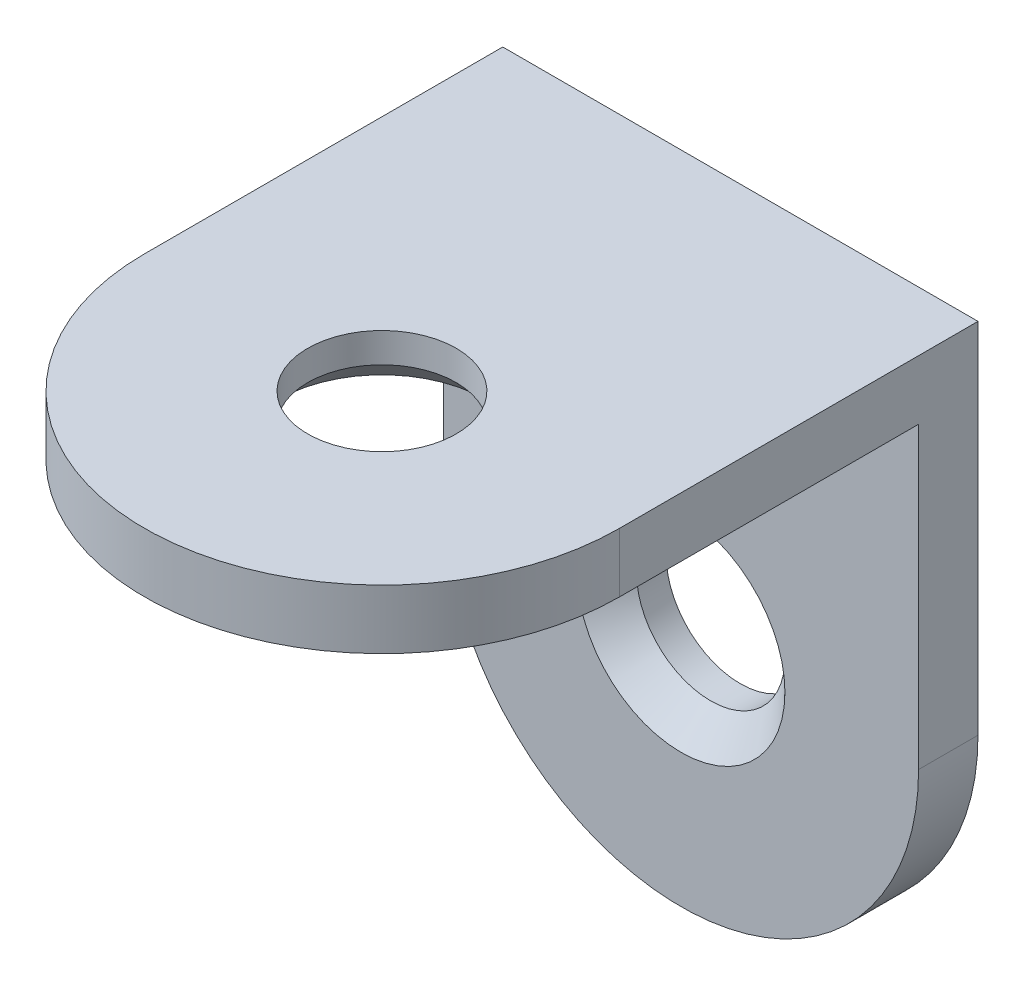
SolidWorks part; units mm, degrees
material "Plain Carbon Steel"
ref_plane "Front Plane" through (0, 0, 0) normal (0, 0, 1) x (1, 0, 0)
ref_plane "Top Plane" through (0, 0, 0) normal (0, 1, 0) x (1, 0, 0)
ref_plane "Right Plane" through (0, 0, 0) normal (1, 0, 0) x (0, 0, -1)
sketch "Sketch2" plane through (0, 0, 0) normal (1, 0, 0) x (0, 0, -1)
  line L0 (-20.07, 0) -> (0, 0)
  line L1 (0, 0) -> (0, -20.07)
  line L2 (0, -20.07) -> (-2, -20.07)
  line L3 (-2, -20.07) -> (-2, -2)
  line L4 (-2, -2) -> (-20.07, -2)
  line L5 (-20.07, -2) -> (-20.07, 0)
  dimension "D1" = 20.07
  dimension "D2" = 20.07
  dimension "D3" = 2
  dimension "D4" = 2
extrude "Boss-Extrude1" add sketch "Sketch2" along normal blind 8.001 and the other way blind 8.001 contours L3 L4 L5 L0 L1 L2
sketch "Sketch3" plane through (0, -2, 0) normal (0, -1, 0) x (1, 0, 0)
  line L0 (0, 0) -> (0, 22.5238) construction
  line L1 (-8.001, 20.07) -> (8.001, 20.07) construction
  line L2 (-8.001, 20.07) -> (8.001, 20.07) construction
  line L4 (-8.001, 12.069) -> (-12.7259, 12.069)
  line L5 (-12.7259, 12.069) -> (-12.7259, 24.9157)
  line L6 (-12.7259, 24.9157) -> (12.142, 24.9157)
  line L7 (12.142, 24.9157) -> (12.142, 12.069)
  line L8 (12.142, 12.069) -> (8.001, 12.069)
  arc A0 (8.001, 12.069) -> (-8.001, 12.069) centre (0, 12.069) ccw
  dimension "D1" = 16.002
extrude "Cut-Extrude1" cut sketch "Sketch3" against normal blind 8.001
sketch "Sketch4" plane through (0, 0, 2) normal (0, 0, 1) x (1, 0, 0)
  line L0 (0, 0) -> (0, -22.6417) construction
  line L1 (-8.001, -20.07) -> (8.001, -20.07) construction
  line L2 (-8.001, -20.07) -> (8.001, -20.07) construction
  line L4 (-8.001, -12.069) -> (-10.4809, -12.069)
  line L5 (-10.4809, -12.069) -> (-10.4809, -22.6417)
  line L6 (-10.4809, -22.6417) -> (9.893, -22.6417)
  line L7 (9.893, -22.6417) -> (9.893, -12.069)
  line L8 (9.893, -12.069) -> (8.001, -12.069)
  arc A0 (-8.001, -12.069) -> (8.001, -12.069) centre (0, -12.069) ccw
  dimension "D1" = 16.002
extrude "Cut-Extrude2" cut sketch "Sketch4" against normal blind 8.001
sketch "Sketch5" plane through (0, 0, 2) normal (0, 0, 1) x (1, 0, 0)
  arc A0 (-8.001, -12.069) -> (8.001, -12.069) centre (0, -12.069) ccw construction
  arc A1 (-8.001, -12.069) -> (8.001, -12.069) centre (0, -12.069) ccw construction
  circle A2 centre (0, -12.069) radius 2.5
  dimension "D1" = 5
extrude "Cut-Extrude3" cut sketch "Sketch5" against normal blind 10 contours A2
sketch "Sketch6" plane through (0, -2, 0) normal (0, -1, 0) x (1, 0, 0)
  arc A0 (8.001, 12.069) -> (-8.001, 12.069) centre (0, 12.069) ccw construction
  arc A1 (8.001, 12.069) -> (-8.001, 12.069) centre (0, 12.069) ccw construction
  circle A2 centre (0, 12.069) radius 2.5
  dimension "D1" = 5
extrude "Cut-Extrude4" cut sketch "Sketch6" against normal blind 10
chamfer "Chamfer1" distance 1 angle 45 2 edges at (0, -2, 9.569) (2.5, -12.069, 2)
